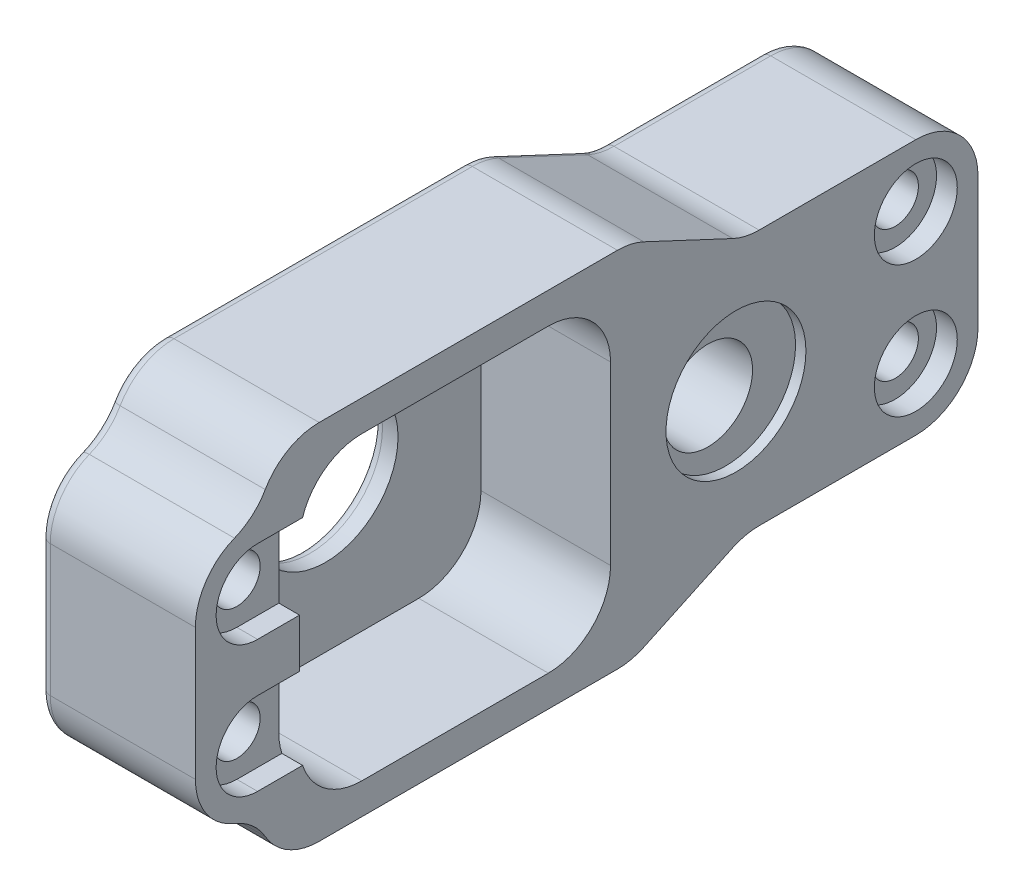
SolidWorks part; units mm, degrees
ref_plane "Front Plane" through (0, 0, 0) normal (0, 0, 1) x (1, 0, 0)
ref_plane "Top Plane" through (0, 0, 0) normal (0, 1, 0) x (1, 0, 0)
ref_plane "Right Plane" through (0, 0, 0) normal (1, 0, 0) x (0, 0, -1)
sketch "Sketch1" plane through (0, 0, 0) normal (1, 0, 0) x (0, 0, -1)
  line L0 (-19.05, 17.5) -> (17, 17.5)
  line L1 (15, 14.5) -> (-15, 14.5)
  line L2 (15, 14.5) -> (15, -14.5)
  line L3 (15, -14.5) -> (-15, -14.5)
  line L4 (-15, 14.5) -> (-15, -14.5)
  line L5 (15, 14.5) -> (-15, -14.5) construction
  line L6 (15, -14.5) -> (-15, 14.5) construction
  line L7 (17, 17.5) -> (28, 12.35)
  line L8 (28, 12.35) -> (50.45, 12.35)
  line L9 (50.45, 12.35) -> (50.45, -12.35)
  line L10 (50.45, -12.35) -> (28, -12.35)
  line L11 (28, -12.35) -> (17, -17.5)
  line L12 (17, -17.5) -> (-19.05, -17.5)
  line L17 (-25.05, 12.35) -> (-25.05, -12.35)
  line L19 (-25.05, 12.35) -> (-19.05, 12.35)
  line L20 (-19.05, 12.35) -> (-19.05, 17.5)
  line L21 (-25.05, -12.35) -> (-19.05, -12.35)
  line L22 (-19.05, -12.35) -> (-19.05, -17.5)
  circle A0 centre (27.1, 0) radius 6.75
  circle A1 centre (25.4, 0) radius 4.3
  circle A2 centre (0, 0) radius 7
  circle A3 centre (-19.05, 6.35) radius 2.25
  circle A5 centre (44.45, 6.35) radius 2.25
  circle A6 centre (44.45, -6.35) radius 2.25
  circle A7 centre (-19.05, -6.35) radius 2.25
  point P0 (0, 0)
  dimension "D1" = 14
  dimension "D6" = 8.6
  dimension "D7" = 13.5
  dimension "D12" = 4.5
  dimension "D13" = 3
  dimension "D2" = 30
  dimension "D3" = 29
  dimension "D4" = 10.4
  dimension "D5" = 1.7
  dimension "D8" = 2
  dimension "D10" = 19.05
  dimension "D11" = 6.35
  dimension "D15" = 3
  dimension "D16" = 12.7
  dimension "D17" = 63.5
  dimension "D18" = 6
  dimension "D19" = 6
  dimension "D20" = 6
  dimension "D21" = 6
  dimension "D22" = 2
  dimension "D23" = 2
  dimension "D24" = 13
  dimension "D25" = 6
  dimension "D9" = 2
extrude "Boss-Extrude1" add sketch "Sketch1" along normal blind 15 contours L12 L11 L10 L9 L8 L7 L0 A7 A6 A5 A3 A0 L4 L1 L2 L3 | A0 A1 region at (0, 0, -16.2712) region at (0, 0, -20.5409)
extrude "Boss-Extrude2" add sketch "Sketch1<3>" along normal blind 2.5 contours L1 L4 L3 L2 A2 region at (0, 0, -14.5827)
sketch "Sketch1<3>" plane through (0, 0, 0) normal (1, 0, 0) x (0, 0, -1) same geometry as "Sketch1"
extrude "Cut-Extrude1" cut sketch "Sketch1<4>" against normal blind 1 from surface contours A0 A1 region at (0, 0, -20.5409) starting at face at (15, -6.35, 16.8)
sketch "Sketch1<4>" plane through (0, 0, 0) normal (1, 0, 0) x (0, 0, -1) same geometry as "Sketch1"
fillet "Fillet1" radius 6 14 edges at (8.75, -14.5, 15) (8.75, -14.5, -15) (8.75, 14.5, -15) (8.75, 14.5, 15) (7.5, -12.35, -28) (7.5, 12.35, -28) (7.5, 17.5, -17) (7.5, -17.5, -17) (7.5, -17.5, 19.05) (7.5, 17.5, 19.05) (7.5, -12.35, 25.05) (7.5, 12.35, 25.05) (7.5, -12.35, -50.45) (7.5, 12.35, -50.45)
fillet "Fillet2" radius 6 2 edges at (7.5, -12.35, 19.05) (7.5, 12.35, 19.05)
fillet "Fillet3" radius 1 26 edges at (0, 0, -7) (0, 0, -29.7) (0, 16.6949, 16.1127) (0, 12.958, 19.5772) (0, 9.7135, 24.0186) (0, 0, 25.05) (0, -9.7135, 24.0186) (0, -12.958, 19.5772) (0, -16.6949, 16.1127) (0, -17.5, -1.2772) (0, -17.3568, -16.9681) (0, -14.925, -22.5) (0, -12.4932, -28.0319) (0, -12.35, -36.8925) (0, -10.5926, -48.6926) (0, 0, -50.45) (0, 10.5926, -48.6926) (0, 12.35, -36.8925) (0, 12.4932, -28.0319) (0, 14.925, -22.5) (0, 17.3568, -16.9681) (0, 17.5, -1.2772) (0, 6.35, 16.8) (0, 6.35, -46.7) (0, -6.35, -46.7) (0, -6.35, 16.8)
sketch "Sketch2" plane through (15, 0, 0) normal (1, 0, 0) x (0, 0, -1)
  line L0 (-19.05, 10.35) -> (-14.7077, 10.35)
  line L1 (-14.7077, 10.35) -> (-14.7077, 2.35)
  line L2 (-14.7077, 2.35) -> (-19.05, 2.35)
  line L3 (-19.05, -10.35) -> (-14.7077, -10.35)
  line L4 (-14.7077, -10.35) -> (-14.7077, -2.35)
  line L5 (-14.7077, -2.35) -> (-19.05, -2.35)
  arc A0 (-19.05, 10.35) -> (-19.05, 2.35) centre (-19.05, 6.35) ccw
  arc A1 (-19.05, -2.35) -> (-19.05, -10.35) centre (-19.05, -6.35) ccw
  circle A2 centre (44.45, -6.35) radius 4
  circle A3 centre (44.45, 6.35) radius 4
  arc A4 (-9, 14.5) -> (-15, 8.5) centre (-9, 8.5) ccw construction
  arc A5 (-15, -8.5) -> (-9, -14.5) centre (-9, -8.5) ccw construction
  dimension "D1" = 8
extrude "Cut-Extrude2" cut sketch "Sketch2" against normal blind 2
